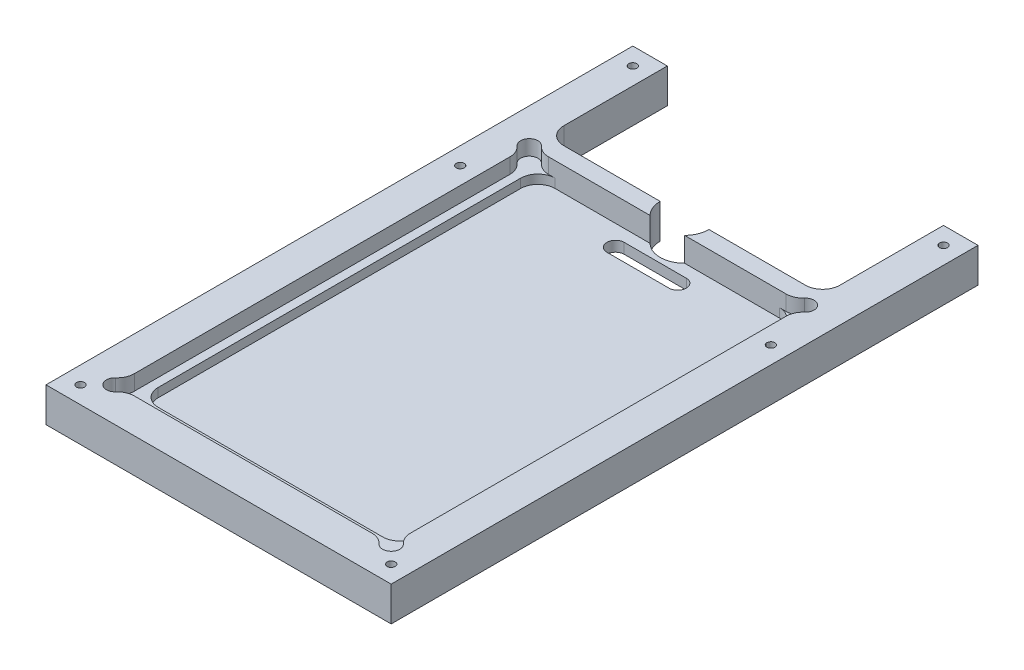
SolidWorks part; units mm, degrees
ref_plane "Front" through (0, 0, 0) normal (0, 0, 1) x (1, 0, 0)
ref_plane "Top" through (0, 0, 0) normal (0, 1, 0) x (1, 0, 0)
ref_plane "Right" through (0, 0, 0) normal (1, 0, 0) x (0, 0, -1)
sketch "Sketch2" plane through (0, 0, 0) normal (0, 1, 0) x (1, 0, 0)
  line L1 (0, 0) -> (127, 0)
  line L2 (0, 0) -> (0, 215.9)
  line L3 (0, 215.9) -> (127, 215.9)
  line L4 (127, 0) -> (127, 215.9)
  dimension "D1" = 215.9
  dimension "D2" = 127
extrude "Boss-Extrude1" add sketch "Sketch2" along normal blind 12.7
sketch "Sketch5" plane through (0, 12.7, 0) normal (0, 1, 0) x (1, 0, 0)
  line L0 (0, 215.9) -> (0, 0) construction
  line L1 (12.7, 12.7) -> (114.3, 12.7)
  line L2 (12.7, 12.7) -> (12.7, 165.1)
  line L3 (12.7, 165.1) -> (114.3, 165.1)
  line L4 (114.3, 12.7) -> (114.3, 165.1)
  line L5 (127, 0) -> (127, 215.9) construction
  line L6 (0, 0) -> (127, 0) construction
  line L7 (127, 215.9) -> (0, 215.9) construction
  dimension "D1" = 12.7
  dimension "D2" = 12.7
  dimension "D3" = 12.7
  dimension "D4" = 50.8
extrude "Cut-Extrude3" cut sketch "Sketch5" against normal blind 5.588
sketch "Sketch6" plane through (0, 12.7, 0) normal (0, 1, 0) x (1, 0, 0)
  line L0 (127, 215.9) -> (0, 215.9) construction
  line L1 (12.7, 215.9) -> (114.3, 215.9)
  line L2 (12.7, 215.9) -> (12.7, 171.45)
  line L3 (12.7, 171.45) -> (114.3, 171.45)
  line L4 (114.3, 215.9) -> (114.3, 171.45)
  line L5 (0, 215.9) -> (0, 0) construction
  line L6 (127, 0) -> (127, 215.9) construction
  line L7 (114.3, 165.1) -> (12.7, 165.1) construction
  dimension "D1" = 12.7
  dimension "D2" = 12.7
  dimension "D3" = 6.35
extrude "Cut-Extrude4" cut sketch "Sketch6" against normal through all
sketch "Sketch8" plane through (0, 12.7, 0) normal (0, 1, 0) x (1, 0, 0)
  line L1 (63.5, 171.45) -> (63.5, 165.1) construction
  line L2 (12.7, 171.45) -> (114.3, 171.45) construction
  line L3 (114.3, 165.1) -> (12.7, 165.1) construction
  line L4 (63.5, 165.1) -> (69.85, 165.1) construction
  circle A1 centre (63.5, 171.45) radius 8.9803
  dimension "D1" = 6.35
extrude "Cut-Extrude6" cut sketch "Sketch8" against normal through all
sketch "Sketch9" plane through (0, 7.112, 0) normal (0, 1, 0) x (1, 0, 0)
  line L0 (57.15, 165.1) -> (12.7, 165.1) construction
  line L1 (15.875, 165.1) -> (111.125, 165.1)
  line L2 (15.875, 165.1) -> (15.875, 19.05)
  line L3 (15.875, 19.05) -> (111.125, 19.05)
  line L4 (111.125, 165.1) -> (111.125, 19.05)
  line L5 (12.7, 165.1) -> (12.7, 12.7) construction
  line L6 (114.3, 12.7) -> (114.3, 165.1) construction
  line L7 (12.7, 12.7) -> (114.3, 12.7) construction
  dimension "D1" = 3.175
  dimension "D2" = 3.175
  dimension "D3" = 6.35
extrude "Cut-Extrude7" cut sketch "Sketch9" against normal blind 3.302
sketch "Sketch11" plane through (0, 3.81, 0) normal (0, 1, 0) x (1, 0, 0)
  line L0 (74.93, 157.48) -> (52.07, 157.48) construction
  line L1 (74.93, 154.305) -> (52.07, 154.305)
  line L2 (74.93, 160.655) -> (52.07, 160.655)
  line L3 (57.15, 165.1) -> (15.875, 165.1) construction
  line L4 (12.7, 165.1) -> (12.7, 12.7) construction
  arc A0 (74.93, 154.305) -> (74.93, 160.655) centre (74.93, 157.48) ccw
  arc A1 (52.07, 160.655) -> (52.07, 154.305) centre (52.07, 157.48) ccw
  point P2 (63.5, 157.48)
  dimension "D2" = 3.175
  dimension "D1" = 22.86
  dimension "D3" = 7.62
  dimension "D4" = 39.37
extrude "Cut-Extrude8" cut sketch "Sketch11" against normal blind 3.81
hole_wizard "#32 (0.116) Diameter Hole1" positions "Sketch12" profile "Sketch13" hole size "#32" standard "ANSI Inch" end condition through all
sketch "Sketch12" plane through (0, 12.7, 0) normal (0, 1, 0) x (1, 0, 0)
  line L0 (0, 215.9) -> (0, 0) construction
  line L1 (12.7, 215.9) -> (0, 215.9) construction
  line L2 (63.5, 0) -> (63.5, 236.2305) construction
  line L3 (0, 0) -> (127, 0) construction
  line L5 (0, 107.95) -> (127, 107.95) construction
  line L6 (127, 0) -> (127, 215.9) construction
  point P0 (6.35, 209.55)
  point P20 (120.65, 209.55)
  point P22 (120.65, 6.35)
  point P23 (6.35, 6.35)
  point P24 (6.35, 209.55)
  point P26 (120.65, 209.55)
  point P34 (6.35, 146.05)
  point P35 (120.65, 146.05)
  dimension "D1" = 6.35
  dimension "D2" = 6.35
  dimension "D3" = 2
sketch "Sketch13" plane through (6.35, 12.7, -209.55) normal (1, 0, 0) x (0, 0, 1)
  line L0 (0, 0) -> (0, 12.7)
  line L1 (0, 12.7) -> (1.4732, 12.7)
  line L2 (1.4732, 12.7) -> (1.4732, 0)
  line L5 (1.4732, 0) -> (0, 0)
  line L11 (0, -6.35) -> (0, 107.95) construction
  dimension "Thru Hole Dia." = 2.9464
  dimension "Thru Hole Depth" = 12.7
sketch "Sketch18" plane through (0, 12.7, 0) normal (0, 1, 0) x (1, 0, 0)
  circle A0 centre (12.7, 165.1) radius 3.175
  circle A1 centre (114.3, 165.1) radius 3.175
  circle A2 centre (114.3, 12.7) radius 3.175
  circle A3 centre (12.7, 12.7) radius 3.175
  dimension "D1" = 6.35
  dimension "D3" = 2
  dimension "D2" = 2
extrude "Cut-Extrude9" cut sketch "Sketch18" against normal blind 5.588
fillet "Fillet5" radius 6.35 8 edges at (12.7, 9.906, -161.925) (15.875, 9.906, -165.1) (12.7, 9.906, -15.875) (15.875, 9.906, -12.7) (111.125, 9.906, -12.7) (114.3, 9.906, -15.875) (114.3, 9.906, -161.925) (111.125, 9.906, -165.1)
fillet "Fillet7" radius 6.35 2 edges at (114.3, 6.35, -171.45) (12.7, 6.35, -171.45)
fillet "Fillet8" radius 6.35 2 edges at (111.125, 5.461, -19.05) (15.875, 5.461, -19.05)
fillet "Fillet10" radius 6.35 1 edges at (111.125, 5.461, -165.1) type face fillet first side face at (111.125, 5.461, -95.25) second side face at (96.0585, 7.874, -165.1)
fillet "Fillet11" radius 6.35 1 edges at (15.875, 5.461, -165.1) type face fillet first side face at (30.9415, 7.874, -165.1) second side face at (15.875, 5.461, -95.25)
